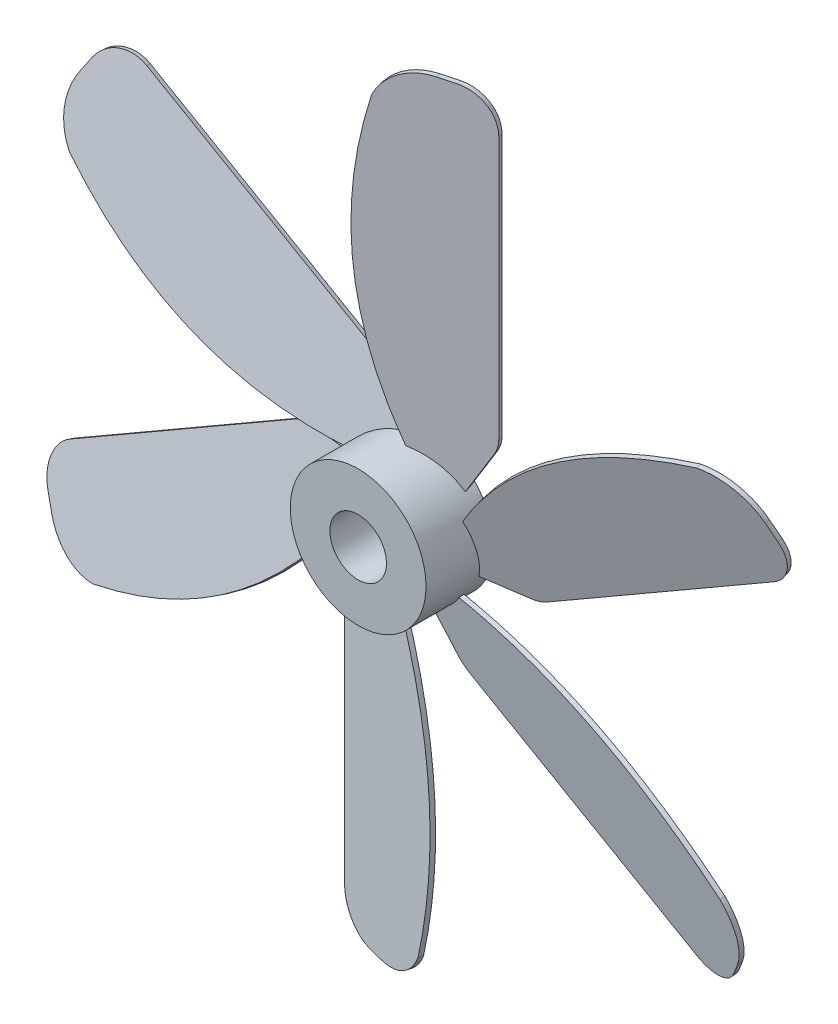
SolidWorks part; units mm, degrees
ref_plane "前视基准面" through (0, 0, 0) normal (0, 0, 1) x (1, 0, 0)
ref_plane "上视基准面" through (0, 0, 0) normal (0, 1, 0) x (1, 0, 0)
ref_plane "右视基准面" through (0, 0, 0) normal (1, 0, 0) x (0, 0, -1)
sketch "草图2" plane through (0, 0, 0) normal (0, 0, 1) x (1, 0, 0)
  circle A0 centre (0, 0) radius 2.5
  circle A1 centre (0, 0) radius 6
  dimension "D1" = 5
  dimension "D2" = 12
extrude "凸台-拉伸1" add sketch "草图2" along normal blind 4
sketch "草图4" plane through (0, 0, 0) normal (0, 1, 0) x (1, 0, 0)
  line L0 (-6, -1.6077) -> (6, 1.6077)
  line L1 (-6, 0) -> (-6, -4) construction
  line L2 (6, -4) -> (6, 0) construction
  line L3 (-6, -4) -> (6, -4) construction
  point P6 (0, 0)
  dimension "D1" = 15
ref_plane "基准面4" through (0, 0, 0) normal (0.2588, 0, 0.9659) x (0.9659, 0, -0.2588)
sketch "草图6" plane through (0, 0, 0) normal (0.2588, 0, 0.9659) x (0.9659, 0, -0.2588)
  line L0 (4, 2.9708) -> (6.6651, 7.5868)
  line L1 (7, 8.8368) -> (7, 32)
  line L2 (4, 35) -> (2.5192, 35)
  arc A0 (2.5192, 35) -> (-2.1784, 32) centre (2.5192, 29.8221) ccw
  arc A1 (7, 32) -> (4, 35) centre (4, 32) ccw
  arc A2 (6.6651, 7.5868) -> (7, 8.8368) centre (4.5, 8.8368) ccw
  ellipse E0 centre (-1.0353, 0) end of major axis (-1.0353, 6) minor radius 5.7956 construction
  ellipse E2 centre (-1.0353, 0) end of major axis (-1.0353, 6) minor radius 5.7956
  ellipse E3 centre (-1.0353, 0) end of major axis (-1.0353, 6) minor radius 5.7956 (4, 2.9708) -> (0.3818, 5.8179) ccw
  spline S0 degree 2 poles (-2.1784, 32) (-6.1316, 18.0744) (0.3818, 5.8179) knots 0 0 0 1 1 1
  point P24 (7, 8.167)
  dimension "D1" = 3
  dimension "D7" = 2.5
  dimension "D10" = 27
  dimension "D11" = 0
  dimension "D2" = 150
  dimension "D3" = 1.4808
  dimension "D4" = 7
  dimension "D5" = 35
  dimension "D6" = 6
  dimension "D8" = 32
  dimension "D9" = 14.5891
extrude "凸台-拉伸2" add sketch "草图6" along normal mid plane 0.4
extrude "凸台-拉伸6" add sketch "草图2<5>" along normal mid plane 4
sketch "草图2<5>" plane through (0, 0, 0) normal (0, 0, 1) x (1, 0, 0) same geometry as "草图2"
pattern_circular "阵列(圆周)1" count 6 over 360 about axis through (0, 0, 4) along (0, 0, -1) of "凸台-拉伸2" reverse direction yes
